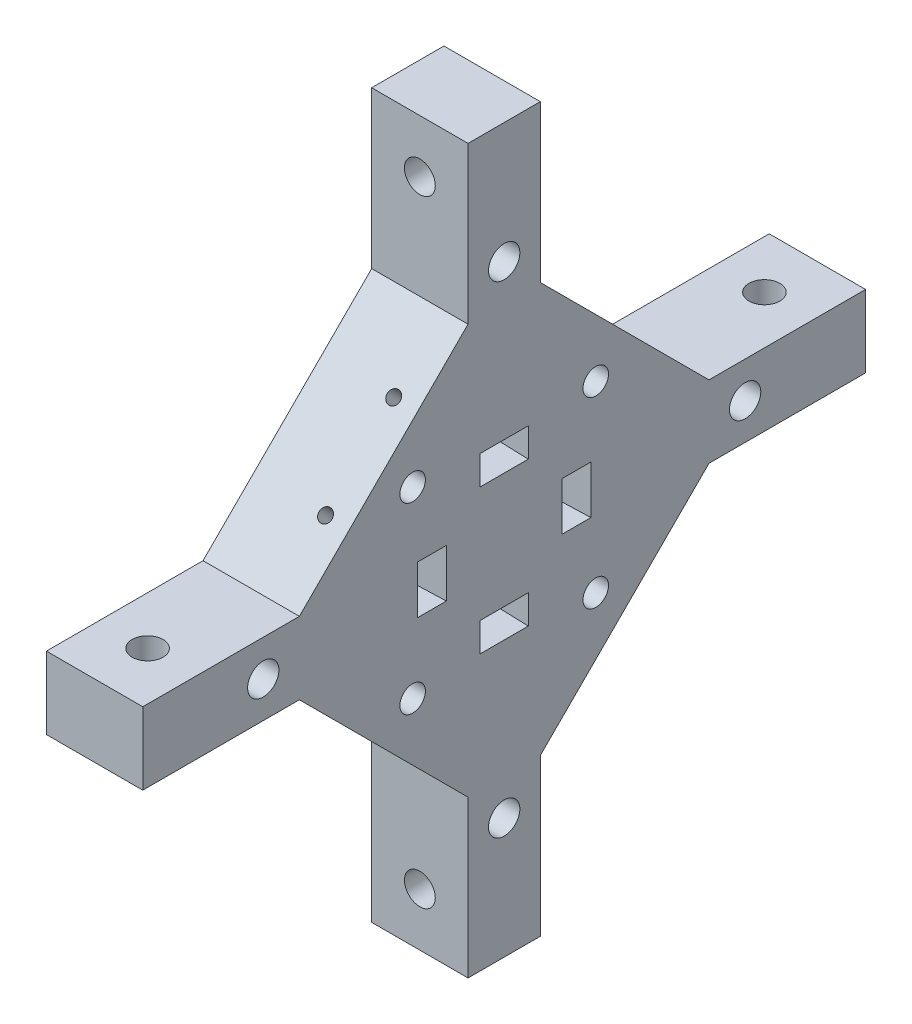
SolidWorks part; units mm, degrees
ref_plane "Front Plane" through (0, 0, 0) normal (0, 0, 1) x (1, 0, 0)
ref_plane "Top Plane" through (0, 0, 0) normal (0, 1, 0) x (1, 0, 0)
ref_plane "Right Plane" through (0, 0, 0) normal (1, 0, 0) x (0, 0, -1)
sketch "Sketch1" plane through (0, 0, 0) normal (1, 0, 0) x (0, 0, -1)
  line L1 (-25, 25) -> (25, 25)
  line L2 (-25, 25) -> (-25, -25)
  line L3 (-25, -25) -> (25, -25)
  line L4 (25, 25) -> (25, -25)
  line L5 (-25, 25) -> (25, -25) construction
  line L6 (-25, -25) -> (25, 25) construction
  circle A0 centre (-19, 19) radius 1.7
  circle A1 centre (19, 19) radius 1.7
  circle A2 centre (19, -19) radius 1.7
  circle A3 centre (-19, -19) radius 1.7
  point P0 (0, 0)
  point P8 (0, 0)
  point P9 (23.2417, -14.3798)
  point P10 (0, 0)
  point P17 (0, 0)
  dimension "D3" = 6
  dimension "D4" = 3.4
  dimension "D1" = 50
  dimension "D2" = 50
extrude "Boss-Extrude1" add sketch "Sketch1" along normal blind 20
sketch "Sketch2" plane through (20, 0, 0) normal (1, 0, 0) x (0, 0, -1)
  circle A0 centre (-19, 19) radius 2.65
  circle A1 centre (19, 19) radius 2.65
  circle A2 centre (19, -19) radius 2.65
  circle A3 centre (-19, -19) radius 2.65
  point P3 (16.6122, 22.4549)
  point P4 (0, 0)
  point P12 (0, 0)
  circle M3 centre (19, -19) radius 1.7
  circle M4 centre (-19, 19) radius 1.7
  circle M9 centre (19, 19) radius 1.7
  circle M10 centre (-19, -19) radius 1.7
  dimension "D1" = 5.3
  dimension "D2" = 4
extrude "Cut-Extrude1" cut sketch "Sketch2" against normal blind 12.5 contours A0 M4 | A1 M9 | A2 M3 | A3 M10 region at (20, 19, 21.575) region at (20, 19, -16.425) region at (20, -19, -16.425) region at (20, -19, 21.575)
sketch "Sketch3" plane through (0, 0, 0) normal (0, 1, 0) x (1, 0, 0)
  line L2 (0, 0) -> (0, 15.125)
  line L3 (0, 25) -> (0, -25) construction
  line L5 (15.125, 0) -> (0, 0)
  line L6 (-993.7626, 0) -> (49006.2374, 0) construction
  arc A1 (0, 15.125) -> (15.125, 0) centre (0, 0) cw
  dimension "D1" = 15.125
revolve "Cut-Revolve1" cut sketch "Sketch3" angle 360 about L6
sketch "Sketch4" plane through (20, 0, 0) normal (1, 0, 0) x (0, 0, -1)
  line L0 (25, 25) -> (42.5, 7.5)
  line L1 (42.5, 7.5) -> (75, 7.5)
  line L2 (75, 7.5) -> (75, -7.5)
  line L3 (75, -7.5) -> (42.5, -7.5)
  line L4 (42.5, -7.5) -> (25, -25)
  line L5 (25, -25) -> (25, 25) construction
  line L6 (25, 25) -> (-25, 25) construction
  line L7 (25, 25) -> (25, -25)
  line L8 (25, -25) -> (7.5, -42.5)
  line L9 (7.5, -42.5) -> (7.5, -75)
  line L10 (7.5, -75) -> (-7.5, -75)
  line L11 (-7.5, -75) -> (-7.5, -42.5)
  line L12 (-7.5, -42.5) -> (-25, -25)
  line L13 (25, -25) -> (-25, -25)
  line L14 (-25, -25) -> (-42.5, -7.5)
  line L15 (-42.5, -7.5) -> (-75, -7.5)
  line L16 (-75, -7.5) -> (-75, 7.5)
  line L17 (-75, 7.5) -> (-42.5, 7.5)
  line L18 (-42.5, 7.5) -> (-25, 25)
  line L19 (-25, -25) -> (-25, 25)
  line L20 (-25, 25) -> (-7.5, 42.5)
  line L21 (-7.5, 42.5) -> (-7.5, 75)
  line L22 (-7.5, 75) -> (7.5, 75)
  line L23 (7.5, 75) -> (7.5, 42.5)
  line L24 (7.5, 42.5) -> (25, 25)
  line L25 (-25, 25) -> (25, 25)
  point P10 (0, 0)
  point P32 (0, 0)
  dimension "D1" = 45
  dimension "D2" = 45
  dimension "D3" = 50
  dimension "D4" = 17.5
  dimension "D5" = 4
extrude "Boss-Extrude3" add sketch "Sketch4" along direction (1, 0, 0) on the side against the normal up to surface (20 mm away) contours L18 L17 L16 L15 L14 | L24 L23 L22 L21 L20 L25 | L4 L3 L2 L1 L0 L24 | L12 L11 L10 L9 L8 region at (20, 0, -44.4428) region at (20, 44.4428, 0) region at (20, -44.4428, 0) region at (20, 0, 44.4428) up to face at (0, 0, 15.125)
sketch "Sketch5" plane through (20, 0, 0) normal (1, 0, 0) x (0, 0, -1)
  line L0 (17, 5) -> (17, -5)
  line L1 (-5, 17) -> (5, 17)
  line L2 (-5, 17) -> (-5, 13)
  line L3 (-5, 13) -> (5, 13)
  line L4 (5, 17) -> (5, 13)
  line L5 (-5, 17) -> (5, 13) construction
  line L6 (-5, 13) -> (5, 17) construction
  line L7 (17, 5) -> (13, 5)
  line L8 (13, 5) -> (13, -5)
  line L9 (17, -5) -> (13, -5)
  line L10 (17, 5) -> (13, -5) construction
  line L11 (13, 5) -> (17, -5) construction
  line L12 (5, -17) -> (-5, -17)
  line L13 (5, -17) -> (5, -13)
  line L14 (5, -13) -> (-5, -13)
  line L15 (-5, -17) -> (-5, -13)
  line L16 (5, -17) -> (-5, -13) construction
  line L17 (5, -13) -> (-5, -17) construction
  line L18 (-17, -5) -> (-17, 5)
  line L19 (-17, -5) -> (-13, -5)
  line L20 (-13, -5) -> (-13, 5)
  line L21 (-17, 5) -> (-13, 5)
  line L22 (-17, -5) -> (-13, 5) construction
  line L23 (-13, -5) -> (-17, 5) construction
  point P0 (0, 15)
  point P5 (0, 0)
  point P7 (15, 0)
  point P14 (0, -15)
  point P19 (-15, 0)
  point P24 (0, 0)
  dimension "D1" = 4
  dimension "D2" = 10
  dimension "D3" = 15
  dimension "D4" = 4
extrude "Cut-Extrude2" cut sketch "Sketch5" against normal blind 8
chamfer "Chamfer1" distance 1 angle 88 8 edges at (20, 0, 13) (20, 0, 17) (20, -13, 0) (20, -17, 0) (20, 13, 0) (20, 17, 0) (20, 0, -13) (20, 0, -17) first distance on face at (20, 15, 0)
sketch "Sketch7" plane through (20, 0, 0) normal (1, 0, 0) x (0, 0, -1)
  line L0 (75, 7.5) -> (75, -7.5) construction
  circle A0 centre (50, 0) radius 3.25
  circle A1 centre (0, -50) radius 3.25
  circle A2 centre (-50, 0) radius 3.25
  circle A3 centre (0, 50) radius 3.25
  point P7 (0, 0)
  point P13 (0, 0)
  dimension "D1" = 6.5
  dimension "D3" = 4
  dimension "D2" = 25
extrude "Cut-Extrude4" cut sketch "Sketch7" against normal through all both and the other way through all
sketch "Sketch8" plane through (0, -7.5, 0) normal (0, -1, 0) x (1, 0, 0)
  line L1 (0, -42.5) -> (0, -75) construction
  line L2 (0, -75) -> (20, -75) construction
  circle A0 centre (10, -64) radius 3.2
  dimension "D1" = 6.4
  dimension "D2" = 10
  dimension "D3" = 11
extrude "Cut-Extrude5" cut sketch "Sketch8" against normal through all both and the other way through all
pattern_circular "CirPattern1" count 4 over 360 about axis through (20, 0, 0) along (1, 0, 0) of "Cut-Extrude5"
sketch "Sketch9" plane through (0, -25, -25) normal (0, -0.7071, -0.7071) x (1, 0, 0)
  line L1 (0, 24.7487) -> (0, -24.7487) construction
  circle A0 centre (15, 10) radius 1.35
  circle A1 centre (15, -10) radius 1.35
  point P7 (0, 0)
  dimension "D1" = 2.7
  dimension "D2" = 15
  dimension "D3" = 10
  dimension "D4" = 2.7
  dimension "D5" = 10
extrude "Cut-Extrude6" cut sketch "Sketch9" against normal blind 15
pattern_circular "CirPattern2" count 4 over 360 about axis through (20, 0, 0) along (1, 0, 0) of "Cut-Extrude6"
